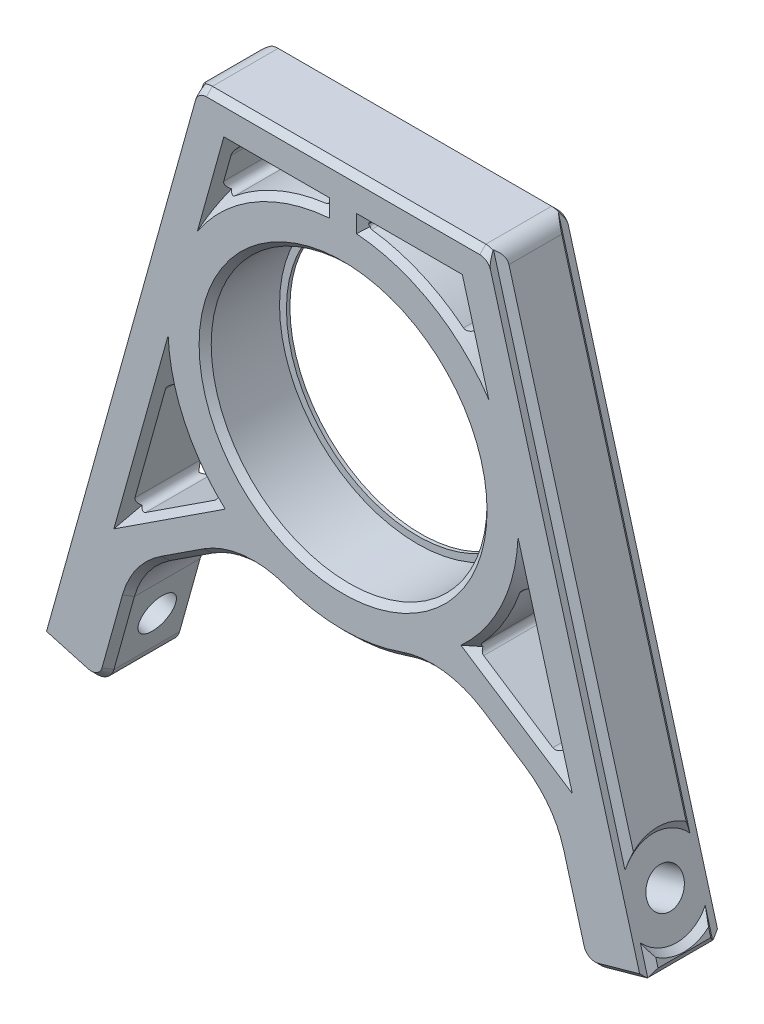
SolidWorks part; units mm, degrees
ref_plane "Front" through (0, 0, 0) normal (0, 0, 1) x (1, 0, 0)
ref_plane "Top" through (0, 0, 0) normal (0, 1, 0) x (1, 0, 0)
ref_plane "Right" through (0, 0, 0) normal (1, 0, 0) x (0, 0, -1)
sketch "Skizze1" plane through (0, 0, 0) normal (0, 0, 1) x (1, 0, 0)
  circle A0 centre (0, 0) radius 15.95
  circle A1 centre (0, 0) radius 20.95
  dimension "D1" = 31.9
  dimension "D2" = 5
extrude "Aufsatz-Linear austragen1" add sketch "Skizze1" along normal blind 9
sketch "Skizze3" plane through (0, 0, 0) normal (0, 0, 1) x (1, 0, 0)
  line L0 (0, 0) -> (23.9187, 0) construction
  line L2 (16.5991, 25.9265) -> (34.4816, -38.2282)
  line L3 (34.4816, -38.2282) -> (27.7386, -40.1077)
  line L4 (27.7386, -40.1077) -> (23.8234, -26.0617)
  line L5 (0, 0) -> (0, 36.4203) construction
  line L6 (16.5991, 25.9265) -> (-16.5991, 25.9265)
  line L7 (23.8234, -26.0617) -> (11.1168, -17.7572)
  line L8 (-23.8234, -26.0617) -> (-11.1168, -17.7572)
  line L9 (-27.7386, -40.1077) -> (-23.8234, -26.0617)
  line L10 (-34.4816, -38.2282) -> (-27.7386, -40.1077)
  line L11 (-16.5991, 25.9265) -> (-34.4816, -38.2282)
  line L12 (-11.1168, -17.7572) -> (11.1168, -17.7572)
  circle A0 centre (0, 0) radius 20.95 construction
  circle A1 centre (0, 0) radius 15.95
  circle A2 centre (0, 0) radius 15.95 construction
  point P13 (0, 25.9265)
  dimension "D1" = 7
extrude "Aufsatz-Linear austragen2" add sketch "Skizze3" along normal up to surface (9 mm away) up to face at (20.95, 0, 9)
sketch "Skizze4" plane through (0, 0, 0) normal (0, 0, -1) x (-1, 0, 0)
  circle A0 centre (0, 0) radius 15.15
  circle A1 centre (0, 0) radius 16.8796
  circle A2 centre (0, 0) radius 15.95 construction
  dimension "D1" = 0.8
extrude "Aufsatz-Linear austragen3" add sketch "Skizze4" against normal blind 0.4
sketch "Skizze6" plane through (-12.3735, -44.3906, 0) normal (-0.2685, -0.9633, 0) x (0.9633, -0.2685, 0)
  line L0 (-22.9509, 4.5) -> (-27.5848, 4.5) construction
  line L1 (-22.9509, 9) -> (-22.9509, 0) construction
  line L2 (-22.9509, 0.75) -> (-22.9509, 8.25)
  line L3 (-22.9509, 8.25) -> (-23.6509, 7.55)
  line L4 (-23.6509, 7.55) -> (-23.6509, 1.45)
  line L5 (-22.9509, 0.75) -> (-23.6509, 1.45)
  point P8 (-23.6509, 4.5)
  dimension "D1" = 7.5
  dimension "D2" = 0.7
  dimension "D3" = 45
extrude "Aufsatz-Linear austragen4" add sketch "Skizze6" against normal up to surface (66.6003 mm away)
sketch "Skizze5" plane through (-15.3652, 4.2829, 0) normal (0.9633, -0.2685, 0) x (0, 0, -1)
  line L0 (-9, -39.5908) -> (0, -39.5908) construction
  line L1 (-9, -46.0829) -> (-9, -31.5014) construction
  line L2 (0, -46.0829) -> (0, -31.5014) construction
  circle A0 centre (-4.5, -39.5908) radius 2.15
  dimension "D1" = 4.3
extrude "Schnitt-Linear austragen1" cut sketch "Skizze5" against normal through all
sketch "Skizze7" plane through (-22.7824, 6.3504, 0) normal (-0.9633, 0.2685, 0) x (0, 0, 1)
  circle A0 centre (4.5, -39.5908) radius 5
  dimension "D1" = 10
extrude "Schnitt-Linear austragen2" cut sketch "Skizze7" against normal blind 0.7
mirror "Spiegeln2" about plane through (0, 0, 0) normal (1, 0, 0) of "Schnitt-Linear austragen1", "Aufsatz-Linear austragen4", "Schnitt-Linear austragen2"
sketch "Skizze8" plane through (0, 0, 9) normal (0, 0, 1) x (1, 0, 0)
  line L0 (25.3323, -21.7914) -> (14.7513, -14.8762)
  line L1 (25.3323, -21.7914) -> (20.4835, -4.3963)
  line L2 (-2.25, 20.8288) -> (-2.25, 21.5265)
  line L3 (11.1168, -17.7572) -> (23.8234, -26.0617) construction
  line L4 (34.4816, -38.2282) -> (16.5991, 25.9265) construction
  line L5 (0, 0) -> (0, -35.1353) construction
  line L6 (-25.3323, -21.7914) -> (-20.4835, -4.3963)
  line L7 (-25.3323, -21.7914) -> (-14.7513, -14.8762)
  line L8 (-13.2578, 21.5265) -> (-15.2558, 14.3583)
  line L10 (-16.5991, 25.9265) -> (-31.8504, -28.7888) construction
  line L11 (16.5991, 25.9265) -> (-16.5991, 25.9265) construction
  line L12 (-16.5991, 25.9265) -> (-34.4816, -38.2282) construction
  line L13 (-2.25, 21.5265) -> (-13.2578, 21.5265)
  line L14 (2.25, 21.5265) -> (13.2578, 21.5265)
  line L15 (13.2578, 21.5265) -> (15.2558, 14.3583)
  line L16 (2.25, 20.8288) -> (2.25, 21.5265)
  arc A0 (20.4835, -4.3963) -> (14.7513, -14.8762) centre (0, 0) cw
  circle A1 centre (0, 0) radius 15.95 construction
  arc A2 (-11.1168, -17.7572) -> (11.1168, -17.7572) centre (0, 0) ccw construction
  arc A3 (-20.4835, -4.3963) -> (-14.7513, -14.8762) centre (0, 0) ccw
  arc A4 (-2.25, 20.8288) -> (-15.2558, 14.3583) centre (0, 0) ccw
  arc A5 (2.25, 20.8288) -> (15.2558, 14.3583) centre (0, 0) cw
  dimension "D1" = 4.4
  dimension "D2" = 4.4
  dimension "D3" = 4.4
  dimension "D4" = 4.4
  dimension "D5" = 2.25
extrude "Schnitt-Linear austragen3" cut sketch "Skizze8" against normal through all
chamfer "Fase1" distance 0.7 angle 45 6 edges at (-32.0702, -26.9702, 4.5) (-34.7553, -36.6029, 4.5) (32.0702, -26.9702, 4.5) (34.7553, -36.6029, 4.5) (35.1559, -38.0402, 4.5) (-35.1559, -38.0402, 4.5)
chamfer "Fase2" distance 0.7 angle 45 1 edges at (15.95, 0, 9)
fillet "Verrundung1" radius 10 4 edges at (23.8234, -26.0617, 4.5) (-23.8234, -26.0617, 4.5) (11.1168, -17.7572, 4.5) (-11.1168, -17.7572, 4.5)
fillet "Verrundung2" radius 2 2 edges at (27.7386, -40.1077, 4.5) (-27.7386, -40.1077, 4.5)
fillet "Verrundung3" radius 2 10 edges at (-16.5991, 25.9265, 8.625) (16.5991, 25.9265, 8.625) (-16.5991, 25.9265, 0.375) (-16.9624, 25.9265, 1.1) (-17.3257, 25.9265, 4.5) (-16.9624, 25.9265, 7.9) (16.5991, 25.9265, 0.375) (17.3257, 25.9265, 4.5) (16.9624, 25.9265, 7.9) (16.9624, 25.9265, 1.1)
chamfer "Fase3" distance 0.7 angle 45 60 edges at (16.2393, 25.8792, 9) (0, 25.9265, 0) (0, 25.9265, 9) (-16.2393, 25.8792, 9) (-32.0734, -38.8995, 0) (-32.0734, -38.8995, 9) (-28.1456, -39.3862, 9) (-26.0179, -33.9346, 9) (-26.0179, -33.9346, 0) (32.0734, -38.8995, 9) (32.0734, -38.8995, 0) (-23.2706, -26.4664, 9) (28.1456, -39.3862, 9) (-18.2295, -22.4058, 9) (-18.2295, -22.4058, 0) (26.0179, -33.9346, 0) (26.0179, -33.9346, 9) (-11.5085, -19.2515, 9) (23.2706, -26.4664, 9) (0, -20.95, 9) (18.2295, -22.4058, 0) (18.2295, -22.4058, 9) (11.5085, -19.2515, 9) (16.2393, 25.8792, 0) (-16.2393, 25.8792, 0) (28.1456, -39.3862, 0) (23.2706, -26.4664, 0) (-28.1456, -39.3862, 0) (11.5085, -19.2515, 0) (-23.2706, -26.4664, 0) (0, -20.95, 0) (-11.5085, -19.2515, 0) (-22.9079, -13.0939, 0) (-20.0418, -18.3338, 0) (-18.3802, -10.0535, 0) (18.3802, -10.0535, 0) (20.0418, -18.3338, 0) (22.9079, -13.0939, 0) (2.25, 21.1776, 0) (9.3317, 18.7569, 0) (7.7539, 21.5265, 0) (14.2568, 17.9424, 0) (-14.2568, 17.9424, 0) (-9.3317, 18.7569, 0) (-2.25, 21.1776, 0) (-7.7539, 21.5265, 0) (2.25, 21.1776, 9) (9.3317, 18.7569, 9) (7.7539, 21.5265, 9) (14.2568, 17.9424, 9) (-9.3317, 18.7569, 9) (-14.2568, 17.9424, 9) (-7.7539, 21.5265, 9) (-2.25, 21.1776, 9) (20.0418, -18.3338, 9) (18.3802, -10.0535, 9) (22.9079, -13.0939, 9) (-20.0418, -18.3338, 9) (-18.3802, -10.0535, 9) (-22.9079, -13.0939, 9)
fillet "Verrundung4" radius 2 2 edges at (13.2578, 21.5265, 4.5) (-13.2578, 21.5265, 4.5)
fillet "Verrundung5" radius 0.8 8 edges at (-25.3323, -21.7914, 4.5) (-14.7513, -14.8762, 4.5) (-20.4835, -4.3963, 4.5) (-15.2558, 14.3583, 4.5) (15.2558, 14.3583, 4.5) (25.3323, -21.7914, 4.5) (14.7513, -14.8762, 4.5) (20.4835, -4.3963, 4.5)
fillet "Verrundung6" radius 0.4 4 edges at (-2.25, 20.8288, 4.5) (-2.25, 21.5265, 4.5) (2.25, 20.8288, 4.5) (2.25, 21.5265, 4.5)
equation "\"D2\"=4"
